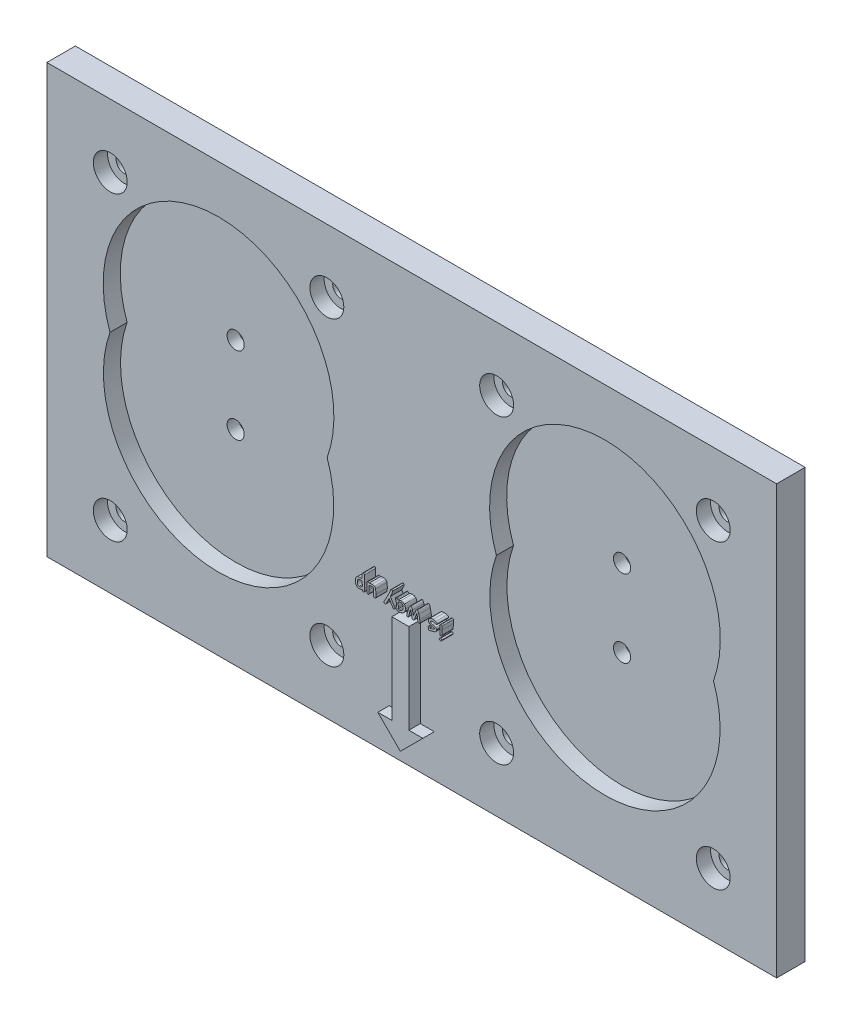
SolidWorks part; units mm, degrees
ref_plane "Front Plane" through (0, 0, 0) normal (0, 0, 1) x (1, 0, 0)
ref_plane "Top Plane" through (0, 0, 0) normal (0, 1, 0) x (1, 0, 0)
ref_plane "Right Plane" through (0, 0, 0) normal (1, 0, 0) x (0, 0, -1)
sketch "Sketch1" plane through (0, 0, 0) normal (0, 0, 1) x (1, 0, 0)
  line L0 (-27, 37) -> (18, 37) construction
  line L1 (-34.62, -30.465) -> (93.4045, -30.465)
  line L2 (-34.62, -30.465) -> (-34.62, 44.62)
  line L3 (-34.62, 44.62) -> (93.4045, 44.62)
  line L4 (93.4045, -30.465) -> (93.4045, 44.62)
  line L6 (18, -22.845) -> (-27, -22.845) construction
  line L7 (29.3923, 47.4436) -> (29.3923, -48.0943) construction
  line L8 (-1.522, 35.265) -> (0.428, 34.861) construction
  line L9 (-22.495, 23.506) -> (-23.167, 21.631) construction
  line L10 (14.167, 21.631) -> (14.645, 19.697) construction
  line L11 (-20.427, -8.82) -> (-22.01, -6.152) construction
  line L12 (13.01, -6.152) -> (11.427, -8.82) construction
  line L13 (-7.593, -16.823) -> (-4.5, -17.07) construction
  circle A0 centre (-4.5, 15.9942) radius 19.4742
  circle A1 centre (63.2846, 15.9942) radius 19.4742
  circle A2 centre (-4.5, 2.4297) radius 19.4378
  circle A3 centre (63.2845, 2.4297) radius 19.4378
  circle A4 centre (-4.5, 15.9942) radius 20.2362
  circle A5 centre (-4.5, 2.4297) radius 20.1998
  circle A6 centre (63.2845, 2.4297) radius 20.1998
  circle A7 centre (63.2846, 15.9942) radius 20.2362
  dimension "D5" = 0.762
  dimension "D6" = 0.762
  dimension "D1" = 7.62
  dimension "D2" = 7.62
  dimension "D3" = 7.62
  dimension "D4" = 7.62
extrude "Boss-Extrude1" add sketch "Sketch1" along normal blind 5 contours L3 L7 L1 L4 A7 A6 | L7 L3 L2 L1 A5 A4 region at (-33.6333, 7.0775, 0) region at (30.379, 7.0775, 0)
sketch "Sketch7" plane through (0, 0, 5) normal (0, 0, 1) x (1, 0, 0)
  circle A0 centre (-23.5006, 33.4996) radius 1.4732
  circle A1 centre (14.4994, 33.5003) radius 1.4732
  circle A2 centre (-23.4996, -19.3454) radius 1.4732
  circle A3 centre (14.5004, -19.3447) radius 1.4732
  circle A4 centre (44.2848, -19.3453) radius 1.4732
  circle A5 centre (44.2842, 33.4997) radius 1.4732
  circle A6 centre (82.2842, 33.5002) radius 1.4732
  circle A7 centre (82.2848, -19.3448) radius 1.4732
  circle A8 centre (-23.5006, 33.4996) radius 1.4732 construction
extrude "Cut-Extrude1" cut sketch "Sketch7" against normal blind 10
sketch "Sketch8" plane through (0, 0, 0) normal (0, 0, -1) x (-1, 0, 0)
  arc A0 (-44.2381, 9.1578) -> (-82.331, 9.1577) centre (-63.2846, 15.9942) ccw
  arc A1 (-44.2381, 9.1578) -> (-82.331, 9.1577) centre (-63.2846, 15.9942) ccw construction
  arc A2 (-82.331, 9.1577) -> (-44.2381, 9.1578) centre (-63.2845, 2.4297) ccw
  arc A3 (-82.331, 9.1577) -> (-44.2381, 9.1578) centre (-63.2845, 2.4297) ccw construction
  circle A4 centre (-63.2845, 2.4297) radius 1.5
  circle A5 centre (-63.2846, 15.9942) radius 1.5
  arc A6 (23.5465, 9.1577) -> (-14.5464, 9.1578) centre (4.5, 15.9942) ccw
  arc A7 (-14.5464, 9.1578) -> (23.5465, 9.1577) centre (4.5, 2.4297) ccw
  arc A8 (-14.5464, 9.1578) -> (23.5465, 9.1577) centre (4.5, 2.4297) ccw construction
  arc A9 (23.5465, 9.1577) -> (-14.5464, 9.1578) centre (4.5, 15.9942) ccw construction
  circle A10 centre (4.5, 15.9942) radius 1.5
  circle A11 centre (4.5, 2.4297) radius 1.5
  dimension "D1" = 3
extrude "Boss-Extrude2" add sketch "Sketch8" against normal blind 2
sketch "Sketch9" plane through (0, 0, 5) normal (0, 0, 1) x (1, 0, 0)
  line L0 (27.8959, -7.3332) -> (27.8959, -23.076)
  line L1 (27.8959, -23.076) -> (25.438, -23.076)
  line L2 (25.438, -23.076) -> (29.3923, -27.0303)
  line L3 (29.3923, -27.0303) -> (33.3466, -23.076)
  line L4 (33.3466, -23.076) -> (30.8886, -23.076)
  line L5 (30.8886, -23.076) -> (30.8886, -7.3332)
  line L6 (30.8886, -7.3332) -> (27.8959, -7.3332)
  line L7 (29.3923, -0.7222) -> (29.3923, -29.3971) construction
  line L8 (-34.62, -30.465) -> (-34.62, 44.62) construction
  line L9 (93.4045, -30.465) -> (93.4045, 44.62) construction
  line L10 (21.3277, -4.2145) -> (37.8326, -4.2145) construction
  text T0 "this way up" font "Comic Sans MS" height in points 9
  point P14 (20.4087, -4.1762)
  point P17 (39.2495, -4.2145)
  point P18 (37.8326, -4.2528)
  point P19 (22.2851, -4.2911)
  point P20 (21.3277, -4.2145)
  point P21 (0, 0)
  point P22 (0, 0)
extrude "Boss-Extrude3" add sketch "Sketch9" along normal blind 2
sketch "Sketch10" plane through (0, 0, 5) normal (0, 0, 1) x (1, 0, 0)
  circle A0 centre (-23.5006, 33.4996) radius 2.9732
  circle A1 centre (14.4994, 33.5003) radius 2.9732
  circle A2 centre (44.2842, 33.4997) radius 2.9732
  circle A3 centre (82.2842, 33.5002) radius 2.9732
  circle A4 centre (-23.4996, -19.3454) radius 2.9732
  circle A5 centre (14.5004, -19.3447) radius 2.9732
  circle A6 centre (44.2848, -19.3453) radius 2.9732
  circle A7 centre (82.2848, -19.3448) radius 2.9732
  circle A9 centre (-23.5006, 33.4996) radius 1.4732 construction
  dimension "D1" = 1.5
extrude "Cut-Extrude4" cut sketch "Sketch10" against normal blind 2.5
